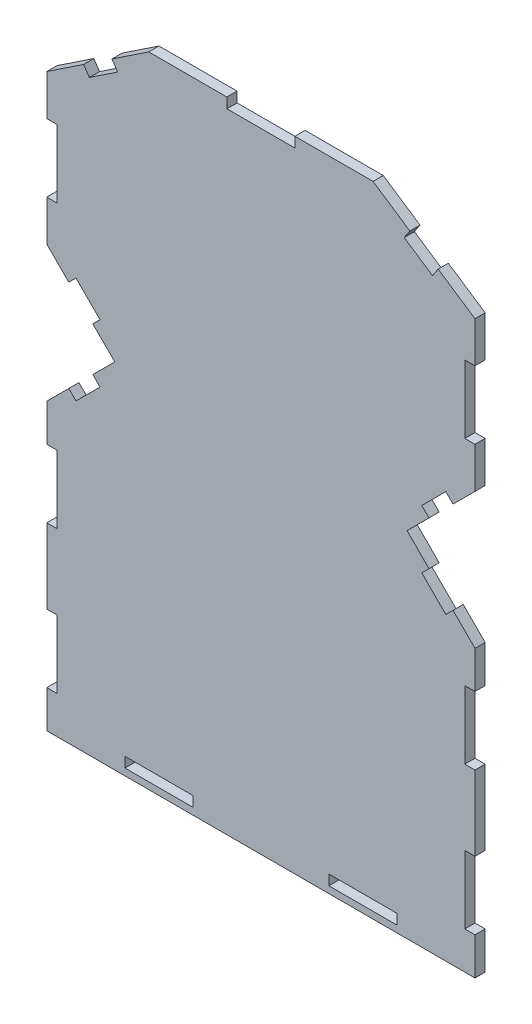
SolidWorks part; units mm, degrees
ref_plane "Front Plane" through (0, 0, 0) normal (0, 0, 1) x (1, 0, 0)
ref_plane "Top Plane" through (0, 0, 0) normal (0, 1, 0) x (1, 0, 0)
ref_plane "Right Plane" through (0, 0, 0) normal (1, 0, 0) x (0, 0, -1)
sketch "Sketch1" plane through (0, 0, 0) normal (0, 0, 1) x (1, 0, 0)
  line L0 (62.2747, 0) -> (62.2747, -11)
  line L1 (-33.7253, 104) -> (-10.7253, 104)
  line L2 (-63.7253, 84) -> (-63.7253, 72)
  line L3 (-63.7253, -84) -> (62.2747, -84)
  line L4 (62.2747, 84) -> (62.2747, 72)
  line L5 (-0.7253, -84) -> (-0.7253, -49.3815) construction
  line L6 (-63.7253, -84) -> (-63.7253, -80.5) construction
  line L7 (-63.7253, -80.5) -> (-60.7253, -80.5) construction
  line L8 (-63.7253, 84) -> (-52.8856, 91.2265)
  line L10 (-63.7253, 84) -> (-63.7253, 72) construction
  line L11 (-60.7253, -80.5) -> (-60.7253, -84) construction
  line L12 (-63.7253, 0) -> (-57.2608, 6.4645)
  line L13 (-43.7253, 20) -> (-50.1898, 26.4645)
  line L14 (62.2747, 0) -> (55.8102, 6.4645)
  line L15 (42.2747, 20) -> (48.7392, 26.4645)
  line L16 (-63.7253, 0) -> (-63.7253, -11)
  line L17 (62.2747, -80.5) -> (59.2747, -80.5) construction
  line L18 (-60.7253, -80.5) -> (59.2747, -80.5) construction
  line L19 (-0.7253, -80.5) -> (-60.7253, -80.5) construction
  line L20 (19.2747, -82) -> (19.2747, -79)
  line L21 (-40.7253, -82) -> (-20.7253, -82)
  line L22 (-40.7253, -82) -> (-40.7253, -79)
  line L23 (-40.7253, -79) -> (-20.7253, -79)
  line L24 (-20.7253, -82) -> (-20.7253, -79)
  line L25 (-40.7253, -82) -> (-20.7253, -79) construction
  line L26 (-40.7253, -79) -> (-20.7253, -82) construction
  line L27 (39.2747, -82) -> (19.2747, -82)
  line L28 (39.2747, -82) -> (39.2747, -79)
  line L29 (39.2747, -79) -> (19.2747, -79)
  line L30 (-63.7253, -84) -> (-62.221, -84) construction
  line L31 (-63.7253, -42) -> (-62.2253, -42) construction
  line L32 (-62.2253, -42) -> (-62.2253, 0) construction
  line L33 (-62.2253, 0) -> (-63.7253, 0) construction
  line L34 (-63.7253, -31) -> (-60.7253, -31)
  line L36 (-63.7253, -11) -> (-60.7253, -11)
  line L37 (-60.7253, -31) -> (-60.7253, -11)
  line L38 (-63.7253, -31) -> (-60.7253, -11) construction
  line L39 (-63.7253, -11) -> (-60.7253, -31) construction
  line L40 (-63.7253, -53) -> (-60.7253, -53)
  line L41 (-60.7253, -53) -> (-60.7253, -73)
  line L42 (-63.7253, -73) -> (-60.7253, -73)
  line L43 (-62.2253, -84) -> (-63.7253, -84) construction
  line L44 (62.2747, -53) -> (59.2747, -53)
  line L45 (59.2747, -53) -> (59.2747, -73)
  line L46 (62.2747, -73) -> (59.2747, -73)
  line L47 (62.2747, -31) -> (59.2747, -31)
  line L48 (62.2747, -11) -> (59.2747, -11)
  line L49 (59.2747, -31) -> (59.2747, -11)
  line L50 (-63.7253, -73) -> (-63.7253, -84)
  line L51 (62.2747, -73) -> (62.2747, -84)
  line L52 (62.2747, -31) -> (62.2747, -53)
  line L53 (-63.7253, -31) -> (-63.7253, -53)
  line L54 (-63.7253, 40) -> (-62.2253, 40) construction
  line L55 (-62.2253, 40) -> (-62.2253, 84) construction
  line L56 (-62.2253, 84) -> (-63.7253, 84) construction
  line L57 (-63.7253, 52) -> (-63.7253, 40)
  line L58 (-63.7253, 52) -> (-60.7253, 52)
  line L60 (-63.7253, 72) -> (-60.7253, 72)
  line L61 (-60.7253, 52) -> (-60.7253, 72)
  line L62 (-63.7253, 52) -> (-60.7253, 72) construction
  line L63 (-63.7253, 72) -> (-60.7253, 52) construction
  line L64 (-63.7253, 52) -> (-63.7253, 40) construction
  line L65 (62.2747, 52) -> (59.2747, 52)
  line L66 (59.2747, 52) -> (59.2747, 72)
  line L67 (62.2747, 72) -> (59.2747, 72)
  line L68 (62.2747, 52) -> (62.2747, 40)
  line L69 (-43.7253, 20) -> (-42.6646, 18.9393) construction
  line L70 (-63.7253, 0) -> (-62.6646, -1.0607) construction
  line L71 (-62.6646, -1.0607) -> (-42.6646, 18.9393) construction
  line L72 (-55.1395, 4.3431) -> (-57.2608, 6.4645)
  line L73 (-55.1395, 4.3431) -> (-48.0685, 11.4142)
  line L75 (-48.0685, 11.4142) -> (-50.1898, 13.5355)
  line L76 (-50.1898, 13.5355) -> (-43.7253, 20)
  line L77 (53.6889, 4.3431) -> (55.8102, 6.4645)
  line L78 (46.6178, 11.4142) -> (48.7392, 13.5355)
  line L79 (53.6889, 4.3431) -> (46.6178, 11.4142)
  line L80 (42.2747, 20) -> (5.8268, 20) construction
  line L81 (-55.1395, 35.6569) -> (-57.2608, 33.5355)
  line L82 (-48.0685, 28.5858) -> (-50.1898, 26.4645)
  line L83 (-55.1395, 35.6569) -> (-48.0685, 28.5858)
  line L84 (-57.2608, 33.5355) -> (-63.7253, 40)
  line L85 (46.6178, 28.5858) -> (48.7392, 26.4645)
  line L86 (53.6889, 35.6569) -> (55.8102, 33.5355)
  line L87 (53.6889, 35.6569) -> (46.6178, 28.5858)
  line L88 (55.8102, 33.5355) -> (62.2747, 40)
  line L89 (48.7392, 13.5355) -> (42.2747, 20)
  line L90 (-63.7253, 84) -> (-52.8856, 91.2265) construction
  line L92 (-52.8856, 91.2265) -> (-51.2215, 88.7303)
  line L93 (-44.5651, 96.7735) -> (-42.901, 94.2774)
  line L94 (-51.2215, 88.7303) -> (-42.901, 94.2774)
  line L95 (-44.5651, 96.7735) -> (-33.7253, 104)
  line L96 (-44.5651, 96.7735) -> (-33.7253, 104) construction
  line L97 (-33.7253, 104) -> (-63.7253, 84) construction
  line L98 (-48.7253, 94) -> (-47.0612, 91.5038) construction
  line L99 (51.4349, 91.2265) -> (49.7708, 88.7303)
  line L100 (49.7708, 88.7303) -> (41.4503, 94.2774)
  line L101 (43.1144, 96.7735) -> (41.4503, 94.2774)
  line L102 (32.2747, 104) -> (43.1144, 96.7735)
  line L103 (62.2747, 84) -> (51.4349, 91.2265)
  line L104 (-33.7253, 104) -> (-33.7253, 102.5) construction
  line L105 (-33.7253, 102.5) -> (32.2747, 102.5) construction
  line L106 (32.2747, 102.5) -> (32.2747, 104) construction
  line L107 (-10.7253, 101) -> (9.2747, 101)
  line L108 (-10.7253, 101) -> (-10.7253, 104)
  line L110 (9.2747, 101) -> (9.2747, 104)
  line L111 (-10.7253, 101) -> (9.2747, 104) construction
  line L112 (-10.7253, 104) -> (9.2747, 101) construction
  line L113 (9.2747, 104) -> (32.2747, 104)
  point P0 (0, 0)
  point P20 (-30.7253, -80.5)
  point P31 (-62.2253, -21)
  point P53 (-62.2253, 62)
  point P67 (-52.6646, 8.9393)
  point P94 (-0.7253, 102.5)
  dimension "D1" = 84
  dimension "D2" = 126
  dimension "D3" = 20
  dimension "D4" = 30
  dimension "D5" = 20
  dimension "D6" = 20
  dimension "D7" = 44
  dimension "D8" = 20
  dimension "D9" = 30
  dimension "D10" = 20
  dimension "D11" = 20
  dimension "D12" = 84
  dimension "D13" = 44
  dimension "D14" = 20
  dimension "D15" = 3
  dimension "D16" = 3.5
  dimension "D17" = 20
  dimension "D18" = 3
  dimension "D19" = 1.5
  dimension "D20" = 20
  dimension "D21" = 3
  dimension "D22" = 1.5
  dimension "D23" = 1.5
  dimension "D24" = 20
  dimension "D25" = 3
  dimension "D26" = 10
  dimension "D27" = 1.5
  dimension "D28" = 48.0685
  dimension "D29" = 10
  dimension "D30" = 3
  dimension "D32" = 20
  dimension "D33" = 3
extrude "Boss-Extrude1" add sketch "Sketch1" along normal blind 3
